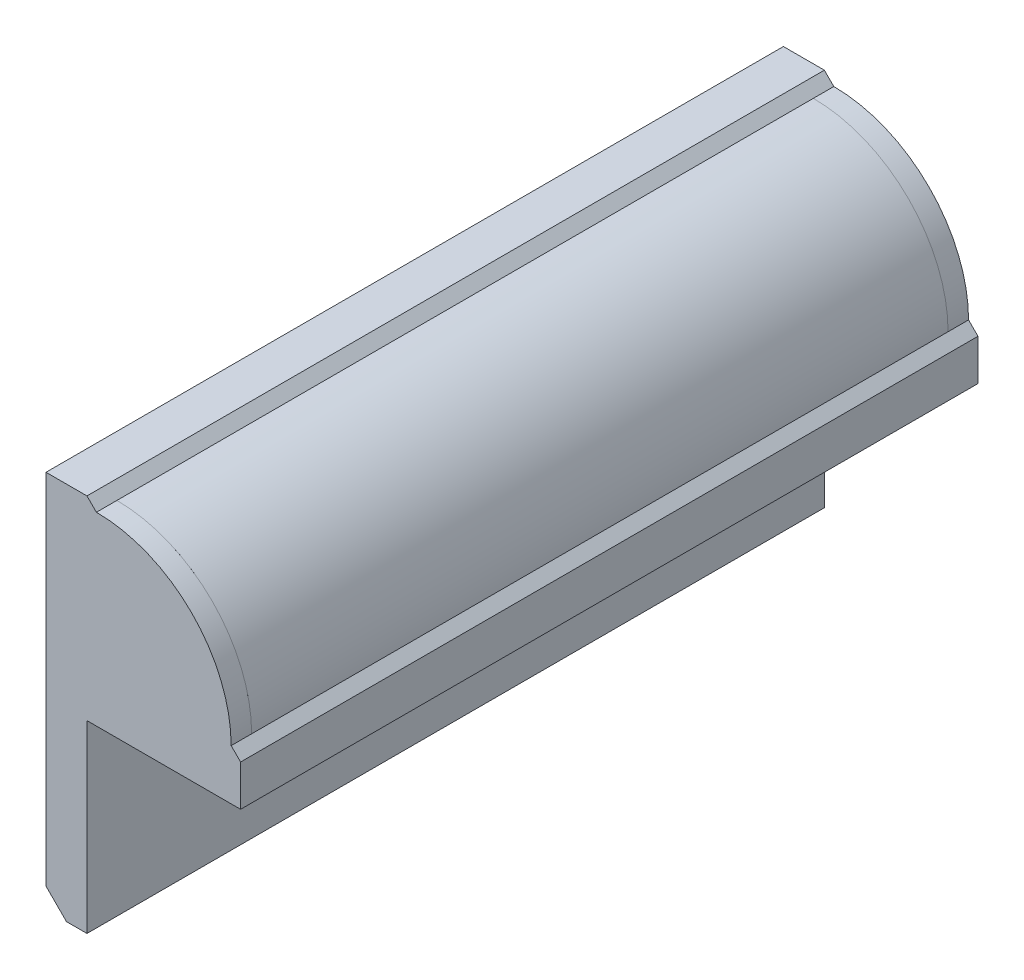
SolidWorks part; units mm, degrees
material "POM Ацеталь кополимер"
ref_plane "Спереди" through (0, 0, 0) normal (0, 0, 1) x (1, 0, 0)
ref_plane "Сверху" through (0, 0, 0) normal (0, 1, 0) x (1, 0, 0)
ref_plane "Справа" through (0, 0, 0) normal (1, 0, 0) x (0, 0, -1)
sketch "Эскиз1" plane through (0, 0, 0) normal (0, 0, 1) x (1, 0, 0)
  line L0 (0, 0) -> (7.5, 0)
  line L1 (7.5, 0) -> (7.5, 2)
  line L3 (-2, 9.5) -> (0, 9.5)
  line L7 (0, 9.5) -> (7.5, 2)
  line L8 (0, 0) -> (0, -9)
  line L9 (0, -9) -> (-2, -9)
  line L10 (-2, -9) -> (-2, 9.5)
  dimension "D1" = 45
  dimension "D2" = 2
  dimension "D3" = 7.5
  dimension "D4" = 2
  dimension "D5" = 9
  dimension "D6" = 2
extrude "База" add sketch "Эскиз1" along normal mid plane 34
sketch "Эскиз4" plane through (0, 0, 17) normal (0, 0, 1) x (1, 0, 0)
  line L0 (6.5784, 2.9216) -> (0.9216, 8.5784)
  line L1 (7.5, 2) -> (0, 9.5) construction
  line L2 (0.9216, 8.5784) -> (-1.1997, 6.4571)
  line L3 (-1.1997, 6.4571) -> (4.4571, 0.8003)
  line L4 (4.4571, 0.8003) -> (6.5784, 2.9216)
  point P4 (3.75, 5.75)
  point P7 (3.75, 5.75)
  dimension "D1" = 3
  dimension "D2" = 8
  dimension "D3" = 8
extrude "Плата" cut sketch "Эскиз4" against normal through all
hole_wizard "Крепление-M2" positions "Эскиз7" profile "Эскиз6" countersink size "M2" standard "DIN" end condition through all
sketch "Эскиз7" plane through (-2, 0, 0) normal (-1, 0, 0) x (0, 0, 1)
  line L0 (-11.25, -5) -> (0, -5) construction
  line L1 (0, -5) -> (11.25, -5) construction
  point P0 (-11.25, -5)
  point P2 (11.25, -5)
  dimension "D1" = 22.5
  dimension "D2" = 5
sketch "Эскиз6" plane through (-2, -5, -11.25) normal (0, 1, 0) x (0, 0, 1)
  line L0 (0, 0) -> (0, 9.5)
  line L1 (0, 9.5) -> (1.2, 9.5)
  line L2 (1.2, 9.5) -> (1.2, 1)
  line L3 (1.2, 1) -> (2.2, 0)
  line L5 (2.2, 0) -> (0, 0)
  line L6 (-1.2, 1) -> (-2.2, 0) construction
  line L11 (0, -6.35) -> (0, 107.95) construction
  dimension "Диаметр сквозного отверстия" = 2.4
  dimension "Глубина сквозного отверстия" = 9.5
  dimension "Диаметр передней зенковки" = 4.4
  dimension "Угол передней зенковки" = 90
chamfer "Фаска2" distance 1 angle 45 1 edges at (-2, -9, 0)
sketch "Эскиз9" plane through (0, 0, 17) normal (0, 0, 1) x (1, 0, 0)
  line L11 (0.4608, 9.0392) -> (-0.5392, 9.0392)
  line L12 (0.9216, 8.5784) -> (0, 9.5) construction
  line L13 (-0.5392, 9.0392) -> (-0.5392, 7.1176)
  line L14 (0.9216, 8.5784) -> (-1.1997, 6.4571) construction
  line L15 (-0.5392, 7.1176) -> (0.9216, 8.5784)
  line L16 (0.9216, 8.5784) -> (0.4608, 9.0392)
  line L17 (6.5784, 2.9216) -> (7.0392, 2.4608)
  line L18 (7.5, 2) -> (6.5784, 2.9216) construction
  line L19 (7.0392, 2.4608) -> (7.0392, 1.4608)
  line L20 (7.0392, 1.4608) -> (5.1176, 1.4608)
  line L21 (4.4571, 0.8003) -> (6.5784, 2.9216) construction
  line L22 (5.1176, 1.4608) -> (6.5784, 2.9216)
  dimension "D1" = 1
extrude "Вырез-Вытянуть2" cut sketch "Эскиз9" against normal through all
sketch "Эскиз12" plane through (0, 0, -17) normal (0, 0, -1) x (-1, 0, 0)
  line L0 (-7.0392, 2.4608) -> (-7.5, 2)
  line L1 (-7.5, 2) -> (-7.5, 0)
  line L2 (-7.5, 0) -> (0, 0)
  line L3 (0, 0) -> (0, -9)
  line L4 (0, -9) -> (1, -9)
  line L5 (1, -9) -> (2, -8)
  line L6 (2, -8) -> (2, 9.5)
  line L7 (2, 9.5) -> (0, 9.5)
  line L8 (0, 9.5) -> (-0.4608, 9.0392)
  arc A0 (-7.0392, 2.4608) -> (-0.4608, 9.0392) centre (-0.4592, 2.4592) cw
  dimension "D1" = 6.58
extrude "Стенка-1" add sketch "Эскиз12" along normal blind 1
sketch "Эскиз13" plane through (0, 0, 17) normal (0, 0, 1) x (1, 0, 0)
  line L0 (7.0392, 2.4608) -> (7.5, 2)
  line L1 (7.5, 2) -> (7.5, 0)
  line L2 (7.5, 0) -> (0, 0)
  line L3 (0, 0) -> (0, -9)
  line L4 (0, -9) -> (-1, -9)
  line L5 (-1, -9) -> (-2, -8)
  line L6 (-2, -8) -> (-2, 9.5)
  line L7 (-2, 9.5) -> (0, 9.5)
  line L8 (0, 9.5) -> (0.4608, 9.0392)
  arc A0 (0.4608, 9.0392) -> (7.0392, 2.4608) centre (0.4592, 2.4592) cw
  dimension "D1" = 6.58
extrude "Стенка-2" add sketch "Эскиз13" along normal blind 1
sketch "Эскиз10" plane through (0, 0, 17) normal (0, 0, -1) x (-1, 0, 0)
  line L8 (-0.4608, 9.0392) -> (-0.4608, 8.0392)
  line L12 (-7.0392, 2.4608) -> (-6.0392, 2.4608)
  arc A4 (-0.4608, 9.0392) -> (-7.0392, 2.4608) centre (-0.4592, 2.4592) ccw construction
  arc A5 (-0.4608, 9.0392) -> (-7.0392, 2.4608) centre (-0.4608, 2.4608) ccw
  arc A6 (-0.4608, 8.0392) -> (-6.0392, 2.4608) centre (-0.4608, 2.4608) ccw
  dimension "D1" = 1
extrude "Рассеиватель" add sketch "Эскиз10" along normal up to surface (34 mm away) separate body up to face at (2.8997, 4.8997, -17)
fillet "Скругление12" radius 0.75 8 edges at (4.7874, 1.1305, 17) (4.7874, 1.1305, -17) (-0.8695, 6.7874, -17) (-0.8695, 6.7874, 17) (7.0392, 1.9608, 17) (7.0392, 1.9608, -17) (-0.0392, 9.0392, -17) (-0.0392, 9.0392, 17)
